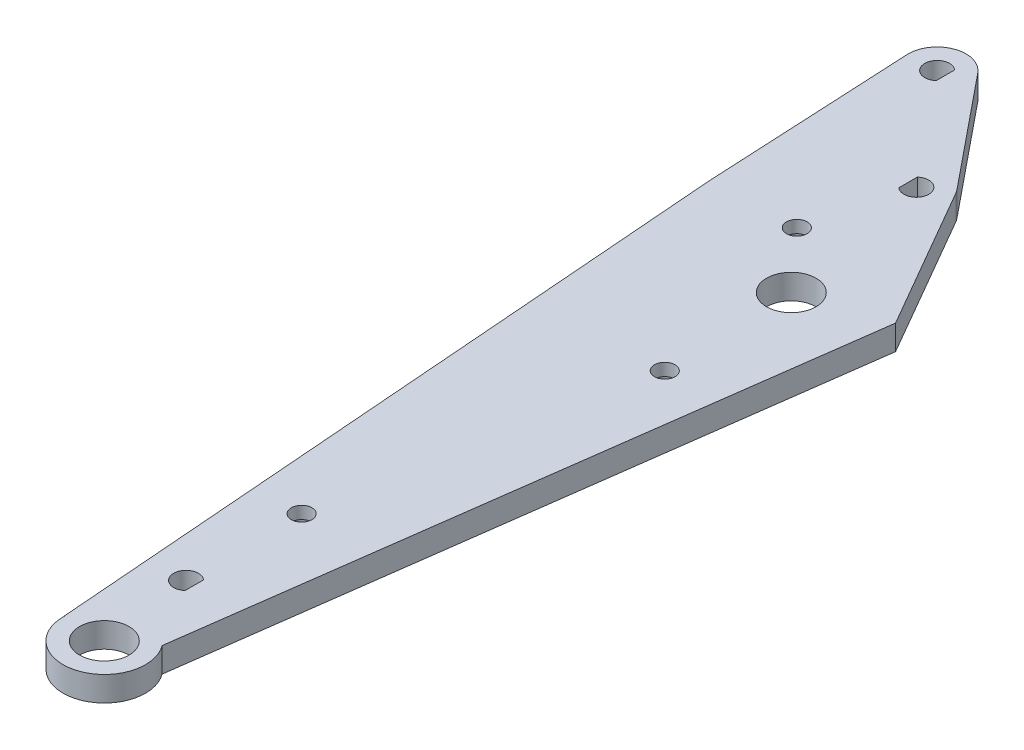
SolidWorks part; units mm, degrees
note: The reader was unsure of these and kept them because the rebuilt part matched: shared geometry of "草图4<3>", "草图4<4>", "草图6<3>".
ref_plane "前视基准面" through (0, 0, 0) normal (0, 0, 1) x (1, 0, 0)
ref_plane "上视基准面" through (0, 0, 0) normal (0, 1, 0) x (1, 0, 0)
ref_plane "右视基准面" through (0, 0, 0) normal (1, 0, 0) x (0, 0, -1)
other "Configuration Table"
sketch "草图2" plane through (0, 0, 0) normal (0, 1, 0) x (1, 0, 0)
  line L8 (-15.2382, -15.3821) -> (-8, 0)
  line L9 (-8, 0) -> (0, 0)
  line L10 (0, 0) -> (10.9793, -19.0167)
  line L11 (10.9793, -19.0167) -> (1.4123, -100.4567) construction
  line L12 (1.4123, -100.4567) -> (-8.6437, -100.1259)
  line L13 (-8.6437, -100.1259) -> (-15.2382, -15.3821)
  line L14 (-15.2382, -15.3821) -> (1.4511, -22.125)
  line L15 (1.35, -100.8754) -> (10.9793, -19.0167)
  line L16 (-3.0207, -2.382) -> (-3.0207, -4.618)
  circle A9 centre (1.4511, -22.125) radius 3
  circle A10 centre (-3.6157, -100.2913) radius 3
  circle A11 centre (-3.6157, -100.2913) radius 5
  circle A12 centre (-2.0207, -3.5) radius 1.5
  circle A13 centre (-2.0207, -3.5) radius 3.5
  point P17 (0, 0)
  dimension "D10" = 18
  dimension "D12" = 6
  dimension "D14" = 3
  dimension "D15" = 2
  dimension "D13" = 6
  dimension "D6" = 2
  dimension "D1" = 8
  dimension "D2" = 13
  dimension "D3" = 17
  dimension "D4" = 85
  dimension "D5" = 82
  dimension "D7" = 120
  dimension "D8" = 115.2
  dimension "D9" = 143.3
  dimension "D11" = 86.8
  dimension "D16" = 1
extrude "凸台-拉伸1" add sketch "草图2" along normal blind 3
sketch "草图3" plane through (0, 0, 0) normal (0, -1, 0) x (1, 0, 0)
  line L5 (-12, -8.882) -> (-12, -11.118)
  circle A0 centre (-13, -10) radius 1.5
  circle A1 centre (-13, -10) radius 3.5
  dimension "D1" = 3
  dimension "D2" = 2
  dimension "D3" = 10
  dimension "D4" = 13
  dimension "D7" = 1
extrude "凸台-拉伸2" add sketch "草图3" against normal up to surface (3 mm away)
sketch "草图4" plane through (0, 0, 0) normal (0, -1, 0) x (1, 0, 0)
  line L0 (-3.9163, 90.0371) -> (-4.0898, 87.8078)
  line L1 (-8.6437, 100.1259) -> (-15.2382, 15.3821) construction
  line L2 (0.3843, 97.2913) -> (10.9793, 19.0167)
  line L3 (1.3994, 100.4562) -> (10.9793, 19.0167) construction
  line L4 (1.0104, 1.75) -> (10.9793, 19.0167) construction
  circle A0 centre (-5, 89) radius 1.5
  circle A1 centre (-5, 89) radius 3.5
  circle A2 centre (-3.6157, 100.2913) radius 5
  circle A3 centre (-3.6157, 100.2913) radius 3 construction
  arc A4 (1.3816, 100.4556) -> (-8.613, 100.1269) centre (-3.6157, 100.2913) ccw construction
  point P14 (0, 0)
  point P20 (10.8518, 20.1019)
  line M11 (1.3994, 100.4562) -> (1.3816, 100.4556)
  line M14 (-8.6437, 100.1259) -> (-15.2382, 15.3821)
  line M25 (10.9793, 19.0167) -> (1.3994, 100.4562)
  dimension "D1" = 3
  dimension "D2" = 2
  dimension "D3" = 89
  dimension "D4" = 5
  dimension "D5" = 1
  dimension "D6" = 4
extrude "凸台-拉伸3" add sketch "草图4" against normal up to surface (3 mm away) contours A1 up to face at (-3.6157, 3, 103.2913)
extrude "切除-拉伸1" cut sketch "草图4<3>" against normal through all contours A0 L0 M14 | A0 M14
sketch "草图4<3>" plane through (0, 0, 0) normal (0, -1, 0) x (1, 0, 0) same geometry as "草图4"
extrude "切除-拉伸2" cut sketch "草图4<4>" against normal through all contours A2 L2 M25 M11
sketch "草图4<4>" plane through (0, 0, 0) normal (0, -1, 0) x (1, 0, 0) same geometry as "草图4"
sketch "草图5" plane through (0, 0, 0) normal (0, -1, 0) x (1, 0, 0)
  line L0 (0.6946, 1.2917) -> (-10.2846, -12.2083)
  line L1 (-16.4957, -9.8256) -> (-15.2382, 15.3821)
  line L2 (-15.2382, 15.3821) -> (-8, 0) construction
  line L5 (-8.6437, 100.1259) -> (-15.2382, 15.3821) construction
  line L6 (-15.2382, 15.3821) -> (-8, 0)
  line L7 (-8, 0) -> (-2.0207, 0) construction
  line L8 (-8, 0) -> (0.6946, 1.2917)
  line L10 (-4, 87.882) -> (-4, 90.118)
  arc A0 (-2.0207, 0) -> (1.0104, 1.75) centre (-2.0207, 3.5) ccw construction
  circle A1 centre (-13, -10) radius 3.5 construction
  circle A2 centre (-13, -10) radius 3.5
  circle A3 centre (-5, 89) radius 1.5
  circle A4 centre (-5, 89) radius 1.5 construction
  point P24 (0, 0)
  point P26 (-2.6145, 87.5565)
  circle M8 centre (-5, 89) radius 1.5
  line M13 (-15.2382, 15.3821) -> (-8, 0)
  line M14 (-8, 0) -> (-2.0207, 0)
  arc M15 (-2.0207, 0) -> (1.0104, 1.75) centre (-2.0207, 3.5) ccw
  dimension "D1" = 1
extrude "凸台-拉伸4" add sketch "草图5" against normal up to surface (3 mm away) contours A2 L0 L1 M15 M14 M13 | L10 M8
sketch "草图6" plane through (0, 0, 0) normal (0, -1, 0) x (1, 0, 0)
  circle A0 centre (-5, 15) radius 2
  circle A1 centre (-5, 15) radius 1.25
  circle A2 centre (2, 38) radius 2
  circle A3 centre (2, 38) radius 1.25
  circle A4 centre (-5, 75) radius 2
  circle A5 centre (-5, 75) radius 1.25
  point P10 (2.7523, 39.9501)
  point P13 (-0.849, 0.7932)
  point P20 (-2.1421, 35.4209)
  dimension "D3" = 4
  dimension "D4" = 2.5
  dimension "D1" = 15
  dimension "D2" = 5
  dimension "D5" = 38
  dimension "D6" = 2
  dimension "D7" = 75
  dimension "D8" = 5
extrude "切除-拉伸3" cut sketch "草图6" against normal through all contours A1 | A3 | A5
extrude "切除-拉伸4" cut sketch "草图6<3>" against normal blind 1.5
sketch "草图6<3>" plane through (0, 0, 0) normal (0, -1, 0) x (1, 0, 0) same geometry as "草图6"
